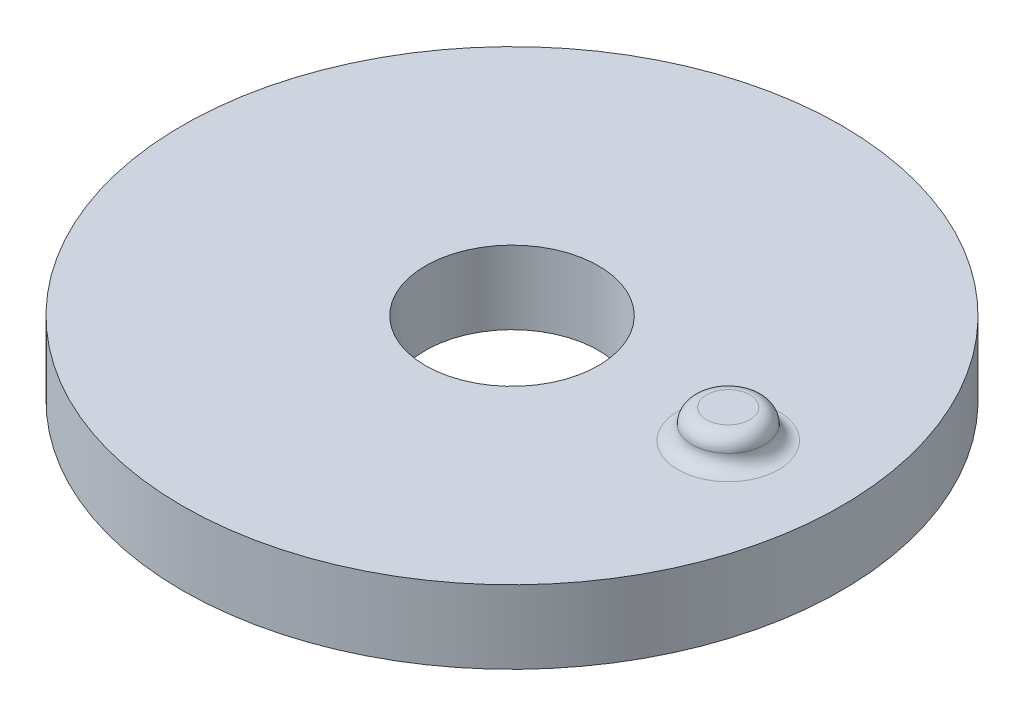
SolidWorks part; units mm, degrees
ref_plane "Front Plane" through (0, 0, 0) normal (0, 0, 1) x (1, 0, 0)
ref_plane "Top Plane" through (0, 0, 0) normal (0, 1, 0) x (1, 0, 0)
ref_plane "Right Plane" through (0, 0, 0) normal (1, 0, 0) x (0, 0, -1)
sketch "Sketch1" plane through (0, 0, 0) normal (0, 1, 0) x (1, 0, 0)
  circle A21 centre (0, 0) radius 114.3
  dimension "D1" = 228.6
extrude "Boss-Extrude1" add sketch "Sketch1" along normal blind 25.4
sketch "Sketch2" plane through (0, 25.4, 0) normal (0, 1, 0) x (1, 0, 0)
  circle A9 centre (75, 0) radius 12.5
  dimension "D1" = 25
  dimension "D2" = 75
extrude "Boss-Extrude2" add sketch "Sketch2" along normal blind 10
fillet "Fillet1" radius 5 2 edges at (75, 25.4, 12.5) (75, 35.4, 12.5)
sketch "Sketch3" plane through (0, 25.4, 0) normal (0, 1, 0) x (1, 0, 0)
  circle A0 centre (0, 0) radius 30
  dimension "D1" = 60
extrude "Cut-Extrude1" cut sketch "Sketch3" against normal through all
